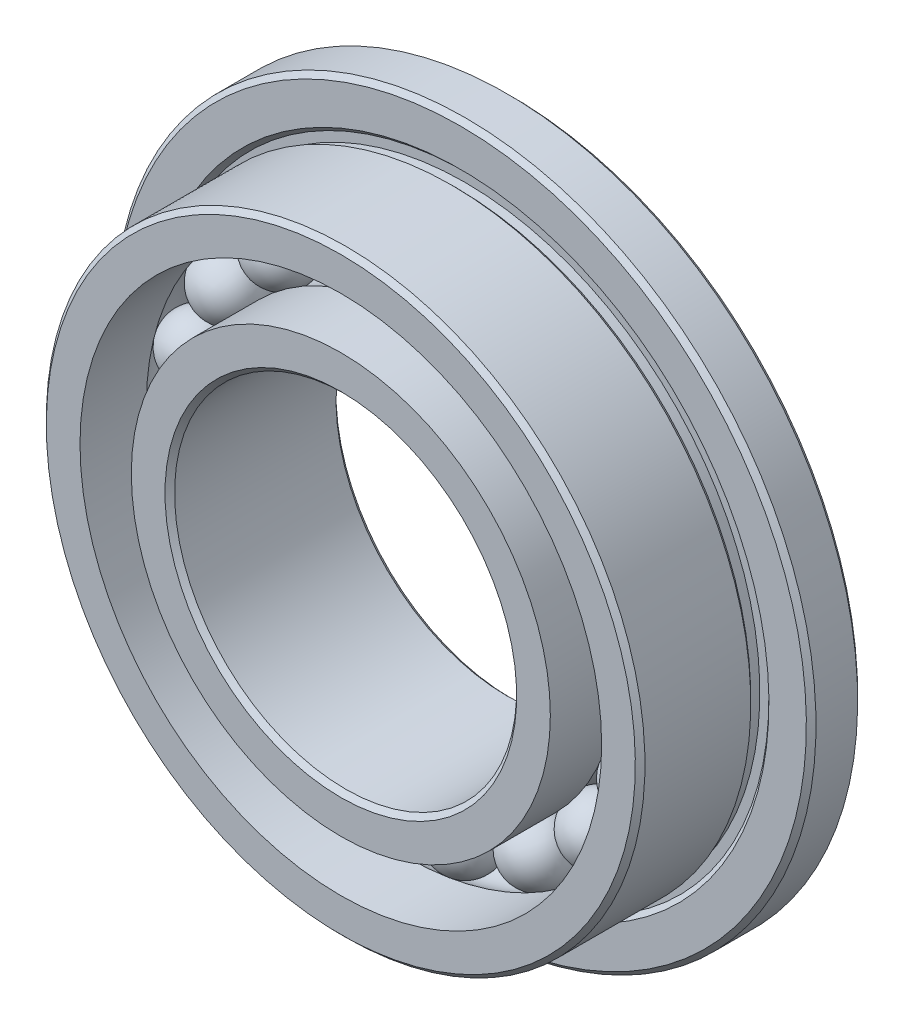
SolidWorks part; units mm, degrees
ref_plane "Front Plane" through (0, 0, 0) normal (0, 0, 1) x (1, 0, 0)
ref_plane "Top Plane" through (0, 0, 0) normal (0, 1, 0) x (1, 0, 0)
ref_plane "Right Plane" through (0, 0, 0) normal (1, 0, 0) x (0, 0, -1)
sketch "Sketch1" plane through (0, 0, 0) normal (1, 0, 0) x (0, 0, -1)
  line L0 (0, 3.5) -> (0, -3.5) construction
  line L1 (-1, 3.5) -> (1, 3.5) construction
  line L2 (0, 0) -> (1, 0) construction
  line L3 (1, 4.1) -> (1, -4.1) construction
  line L4 (1, -4.1) -> (0.4, -4.1) construction
  line L5 (1, 2) -> (0, 2) construction
  line L6 (1, 2) -> (1, -2) construction
  dimension "OD" = 7
  dimension "Width" = 2
  dimension "Flange Thickness" = 0.6
  dimension "ID" = 4
  dimension "Flange OD" = 8.2
sketch "Sketch2" plane through (0, 0, 0) normal (1, 0, 0) x (0, 0, -1)
  line L0 (1, 4.1) -> (0.4, 4.1)
  line L1 (0.4, 4.1) -> (0.4, 3.6061)
  line L2 (0.2939, 3.5) -> (-1, 3.5)
  line L3 (-1, 3.5) -> (-1, 3.05)
  line L4 (-1, 3.05) -> (-0.225, 3.05)
  line L5 (1, 4.1) -> (1, -4.1) construction
  line L6 (1, 3.05) -> (1, 4.1)
  line L7 (1, 2) -> (-1, 2)
  line L8 (-1, 2) -> (-1, 2.45)
  line L9 (-1, 2.45) -> (-0.225, 2.45)
  line L10 (1, 2.45) -> (1, 2)
  line L11 (0, 3.5) -> (0, 2) construction
  line L12 (-0.375, 2.75) -> (0.375, 2.75) construction
  line L13 (0.225, 3.05) -> (1, 3.05)
  line L14 (0.225, 2.45) -> (1, 2.45)
  line L15 (0.4, 3.6061) -> (0.453, 3.553)
  line L16 (0.453, 3.553) -> (0.453, 3.447)
  line L17 (0.453, 3.447) -> (0.347, 3.447)
  line L18 (0.347, 3.447) -> (0.2939, 3.5)
  line L19 (0.4, 3.5) -> (0.453, 3.447) construction
  line L20 (0.453, 3.553) -> (0.347, 3.447) construction
  line L21 (0.2939, 3.5) -> (0.4, 3.5) construction
  line L22 (0.4, 3.5) -> (0.4, 3.6061) construction
  circle A0 centre (0, 2.75) radius 0.375 construction
  arc A1 (-0.225, 3.05) -> (0.225, 3.05) centre (0, 2.75) cw
  arc A2 (-0.225, 2.45) -> (0.225, 2.45) centre (0, 2.75) ccw
  dimension "D1" = 1.5
  dimension "Ball Dia." = 0.75
  dimension "D2" = 135
  dimension "D3" = 0.15
  dimension "D4" = 0.6
  dimension "Race Thikness" = 0.45
revolve "Revolve1" add sketch "Sketch2" angle 360 about L2
fillet "Fillet1" radius 0.0563 3 edges at (0, -4.1, -1) (0, -4.1, -0.4) (0, -3.5, 1) profile chamfer
sketch "Sketch3" plane through (0, 0, 0) normal (0, 0, 1) x (1, 0, 0)
  line L0 (-2, 0) -> (2, 0) construction
  line L1 (-3.5, 0) -> (3.5, 0) construction
  point P5 (0, 0)
  dimension "ID2" = 4
  dimension "OD2" = 7
fillet "Fillet2" radius 0.0563 2 edges at (0, -2, -1) (0, -2, 1) profile chamfer
sketch "Sketch7" plane through (0, 0, 0) normal (0, 0, 1) x (1, 0, 0)
  line L0 (0, 3.125) -> (0, 2.375)
  line L1 (0, 4.1) -> (0, -4.1) construction
  line L2 (-0.4302, 3.125) -> (0, 0) construction
  line L3 (0, 0) -> (0.4302, 3.125) construction
  line L4 (0.4302, 3.125) -> (-0.4302, 3.125) construction
  circle A0 centre (0, 2.75) radius 0.375 construction
  circle A1 centre (0, 0) radius 3.125 construction
  circle A2 centre (0, 0) radius 2.375 construction
  arc A4 (0, 3.125) -> (0, 2.375) centre (0, 2.75) ccw
  dimension "D1" = 15.675
revolve "Revolve3" add sketch "Sketch7" angle 360 about L0
pattern_circular "CirPattern3" count 19 over 360 about axis through (0, 0, 0) along (0, 0, -1) of bodies 107
sketch "Sketch8" plane through (0, 0, 0) normal (1, 0, 0) x (0, 0, -1)
  line L0 (-1, 3.5) -> (1, 3.5) construction
  line L1 (1, 3.5) -> (1, 4.1) construction
  line L2 (-1, -3.5) -> (1, -3.5) construction
  line L3 (1, 4.1) -> (1, -4.1) construction
  dimension "D1" = 7
equation "\"Ball Dia.@Sketch2\" = ( \"OD@Sketch1\" - \"ID@Sketch1\" ) * .25"
equation "\"D3@Sketch2\"=\"Flange Thickness@Sketch1\"/4"
equation "\"D1@Fillet1\" = \"Race Thikness@Sketch2\" / 8"
equation "\"ID2@Sketch3\" = \"ID@Sketch1\""
equation "\"OD2@Sketch3\" = \"OD@Sketch1\""
equation "\"D1@Fillet2\" = \"Race Thikness@Sketch2\" / 8"
equation "\"D1@CirPattern3\"=360/\"D1@Sketch7\"-4"
equation "\"D4@Sketch2\" = ( \"OD@Sketch1\" - \"ID@Sketch1\" ) * .2"
